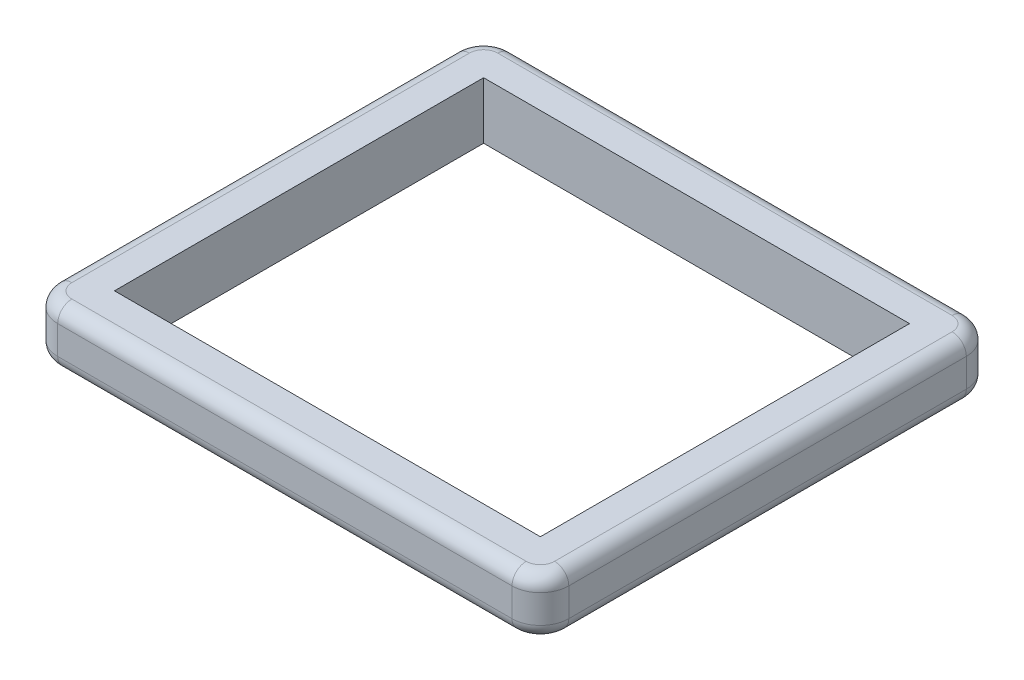
SolidWorks part; units mm, degrees
ref_plane "Front Plane" through (0, 0, 0) normal (0, 0, 1) x (1, 0, 0)
ref_plane "Top Plane" through (0, 0, 0) normal (0, 1, 0) x (1, 0, 0)
ref_plane "Right Plane" through (0, 0, 0) normal (1, 0, 0) x (0, 0, -1)
sketch "Sketch1" plane through (0, 0, 0) normal (0, 1, 0) x (1, 0, 0)
  line L0 (-76.2, -76.2) -> (-76.2, 736.6)
  line L1 (0, 0) -> (762, 0)
  line L2 (0, 0) -> (0, 660.4)
  line L3 (0, 660.4) -> (762, 660.4)
  line L4 (762, 0) -> (762, 660.4)
  line L5 (-76.2, 736.6) -> (838.2, 736.6)
  line L6 (838.2, -76.2) -> (838.2, 736.6)
  line L7 (-76.2, -76.2) -> (838.2, -76.2)
  dimension "D1" = 762
  dimension "D2" = 660.4
  dimension "D3" = 76.2
extrude "Boss-Extrude1" add sketch "Sketch1" along normal blind 101.6
fillet "Fillet1" radius 25.4 4 edges at (381, 101.6, 76.2) (838.2, 101.6, -330.2) (381, 101.6, -736.6) (-76.2, 101.6, -330.2)
fillet "Fillet2" radius 25.4 4 edges at (381, 0, -736.6) (-76.2, 0, -330.2) (381, 0, 76.2) (838.2, 0, -330.2)
fillet "Fillet3" radius 50.8 12 edges at (830.7605, 7.4395, 68.7605) (830.7605, 94.1605, 68.7605) (830.7605, 7.4395, -729.1605) (830.7605, 94.1605, -729.1605) (-68.7605, 7.4395, 68.7605) (-68.7605, 94.1605, 68.7605) (-68.7605, 7.4395, -729.1605) (-68.7605, 94.1605, -729.1605) (-76.2, 50.8, -736.6) (-76.2, 50.8, 76.2) (838.2, 50.8, -736.6) (838.2, 50.8, 76.2)
